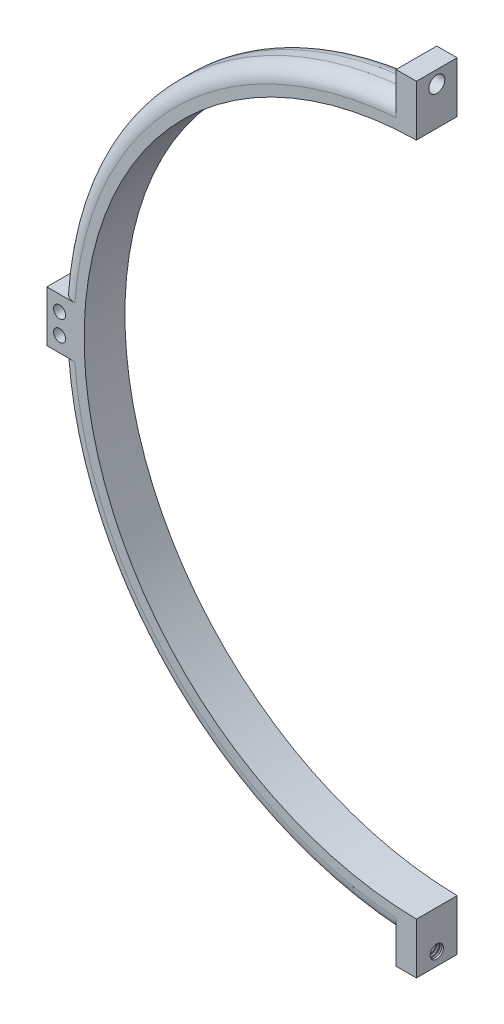
SolidWorks part; units mm, degrees
material "1060 Alloy"
ref_plane "Front Plane" through (0, 0, 0) normal (0, 0, 1) x (1, 0, 0)
ref_plane "Top Plane" through (0, 0, 0) normal (0, 1, 0) x (1, 0, 0)
ref_plane "Right Plane" through (0, 0, 0) normal (1, 0, 0) x (0, 0, -1)
sketch "Sketch1" plane through (0, 0, 0) normal (0, 0, 1) x (1, 0, 0)
  line L0 (0, -84.1375) -> (0, 84.1375) construction
  line L1 (0, 84.1375) -> (0, 96.8375)
  line L2 (0, 96.8375) -> (-6.35, 96.8375)
  line L3 (-6.35, 96.8375) -> (-6.35, 90.2644)
  line L4 (0, -84.1375) -> (0, -96.8375)
  line L5 (0, -96.8375) -> (-6.35, -96.8375)
  line L6 (-6.35, -96.8375) -> (-6.35, -90.2644)
  line L7 (-90.2644, 6.35) -> (-93.4394, 6.35)
  line L8 (-93.4394, 6.35) -> (-93.4394, -6.35)
  line L9 (-93.4394, -6.35) -> (-90.2644, -6.35)
  arc A0 (0, -84.1375) -> (0, 84.1375) centre (0, 0) cw
  arc A1 (-6.35, -90.2644) -> (-90.2644, -6.35) centre (0, 0) cw
  arc A2 (-6.35, 90.2644) -> (-90.2644, 6.35) centre (0, 0) ccw
  point P12 (-93.4394, 0)
  dimension "D1" = 84.1375
  dimension "D3" = 6.35
  dimension "D2" = 12.7
  dimension "D4" = 3.175
  dimension "D5" = 12.7
  dimension "D6" = 6.35
extrude "Boss-Extrude1" add sketch "Sketch1" along normal blind 10.16
sketch "Sketch2" plane through (0, 0, 10.16) normal (0, 0, 1) x (1, 0, 0)
  line L1 (-90.2644, -2.54) -> (-90.2644, 2.54) construction
  line L2 (-6.35, -96.8375) -> (0, -96.8375) construction
  line L3 (0, 96.8375) -> (-1.27, 96.8375)
  line L4 (0, 96.8375) -> (0, -96.8375)
  line L5 (0, -96.8375) -> (-1.27, -96.8375)
  line L6 (-1.27, 96.8375) -> (-1.27, -96.8375)
  circle A0 centre (-90.2644, 2.54) radius 1.5
  circle A1 centre (-90.2644, -2.54) radius 1.5
  point P6 (-90.2644, 0)
  dimension "D1" = 3
  dimension "D2" = 5.08
  dimension "D3" = 1.27
extrude "Cut-Extrude1" cut sketch "Sketch2" against normal through all
sketch "Sketch3" plane through (-1.27, 0, 0) normal (1, 0, 0) x (0, 0, -1)
  line L0 (-10.16, 96.8375) -> (0, 90.4827) construction
  line L1 (0, 96.8375) -> (0, 84.1279) construction
  line L2 (0, -96.8375) -> (-10.16, -96.8375) construction
  circle A0 centre (-5.08, 93.6601) radius 2
  circle A1 centre (-5.08, -93.6625) radius 1.65
  point P8 (-5.08, 93.6601)
  dimension "D1" = 4
  dimension "D3" = 3.3
  dimension "D2" = 3.175
extrude "Cut-Extrude2" cut sketch "Sketch3" against normal through all
thread "Thread1" pitch 0.7 method cut profile "Thread Profile1" start angle 0, offset 0, length 0, pitch 0.7, diameter 3.3
ref_plane "Plane1" through (-1.27, -93.6625, 6.73) normal (0, -1, 0) x (0, 0, 1)
sketch "Thread Profile1" plane through (-1.27, -93.6625, 6.73) normal (0, -1, 0) x (0, 0, 1)
  line L0 (0, 0) -> (0, 0.7) construction
  line L1 (0, 0) -> (0.3789, 0.2187)
  line L2 (0.3789, 0.2187) -> (0.3789, 0.3062)
  line L3 (0.3789, 0.3062) -> (0, 0.525)
  line L4 (0.3789, 0.2625) -> (0, 0.2625) construction
  line L11 (0, 0) -> (0, 0.525)
  point P2 (0, 0)
  dimension "Pitch" = 0.7
  dimension "Profile_Angle" = 60
  dimension "Profile_Land" = 0.0875
  dimension "Profile_Height" = 0.3789
fillet "Fillet3" radius 3.81 4 edges at (-63.9843, 63.9843, 0) (-63.9843, 63.9843, 10.16) (-63.9843, -63.9843, 0) (-63.9843, -63.9843, 10.16)
